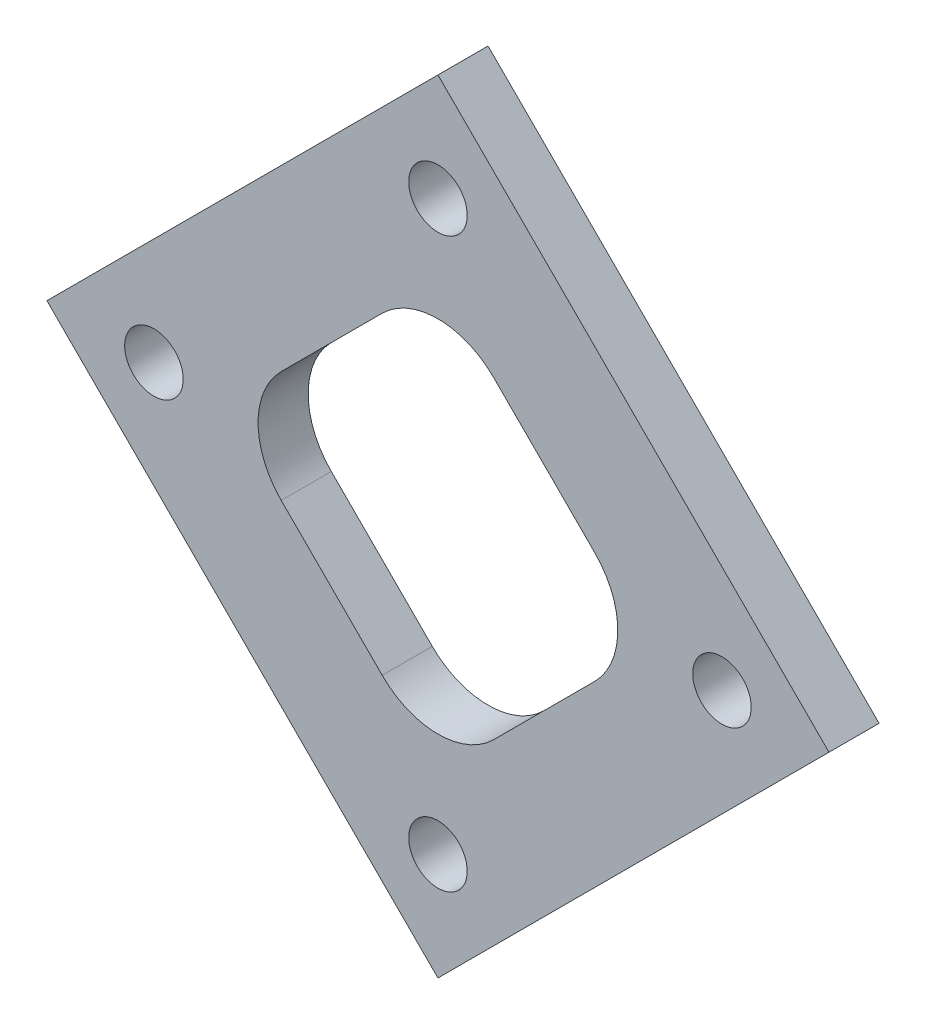
SolidWorks part; units mm, degrees
material "6061-T6 (SS)"
ref_plane "Front" through (0, 0, 0) normal (0, 0, 1) x (1, 0, 0)
ref_plane "Top" through (0, 0, 0) normal (0, 1, 0) x (1, 0, 0)
ref_plane "Right" through (0, 0, 0) normal (1, 0, 0) x (0, 0, -1)
ref_axis "side-side" through (80.9, 0, 0) along (-1, 0, 0)
ref_axis "up-down" through (0, 50, 0) along (0, -1, 0)
ref_axis "front-back" through (0, 0, -80.9) along (0, 0, 1)
sketch "Sketch2" plane through (0, 0, 0) normal (0, 0, 1) x (1, 0, 0)
  line L0 (0, 13.4704) -> (13.4704, 0)
  line L1 (0, 13.4704) -> (-13.4704, 0)
  line L2 (13.4704, 0) -> (0, -13.4704)
  line L3 (-13.4704, 0) -> (0, -13.4704)
  line L4 (0, -50) -> (0, 50) construction
  line L5 (50, 0) -> (-50, 0) construction
  line L6 (0, 24.7841) -> (24.7841, 0)
  line L7 (24.7841, 0) -> (0, -24.7841)
  line L8 (-24.7841, 0) -> (0, -24.7841)
  line L9 (0, 24.7841) -> (-24.7841, 0)
  circle A0 centre (0, 18) radius 1.8542
  circle A1 centre (-18, 0) radius 1.8542
  circle A2 centre (0, -18) radius 1.8542
  circle A3 centre (18, 0) radius 1.8542
  circle A4 centre (0, 0) radius 18 construction
  dimension "D3" = 3.7084
  dimension "D4" = 36
  dimension "D1" = 19.05
  dimension "D2" = 8
extrude "Boss-Extrude1" add sketch "Sketch2" along normal blind 3.175
fillet "Fillet1" radius 5 4 edges at (-13.4704, 0, 1.5875) (0, -13.4704, 1.5875) (13.4704, 0, 1.5875) (0, 13.4704, 1.5875)
